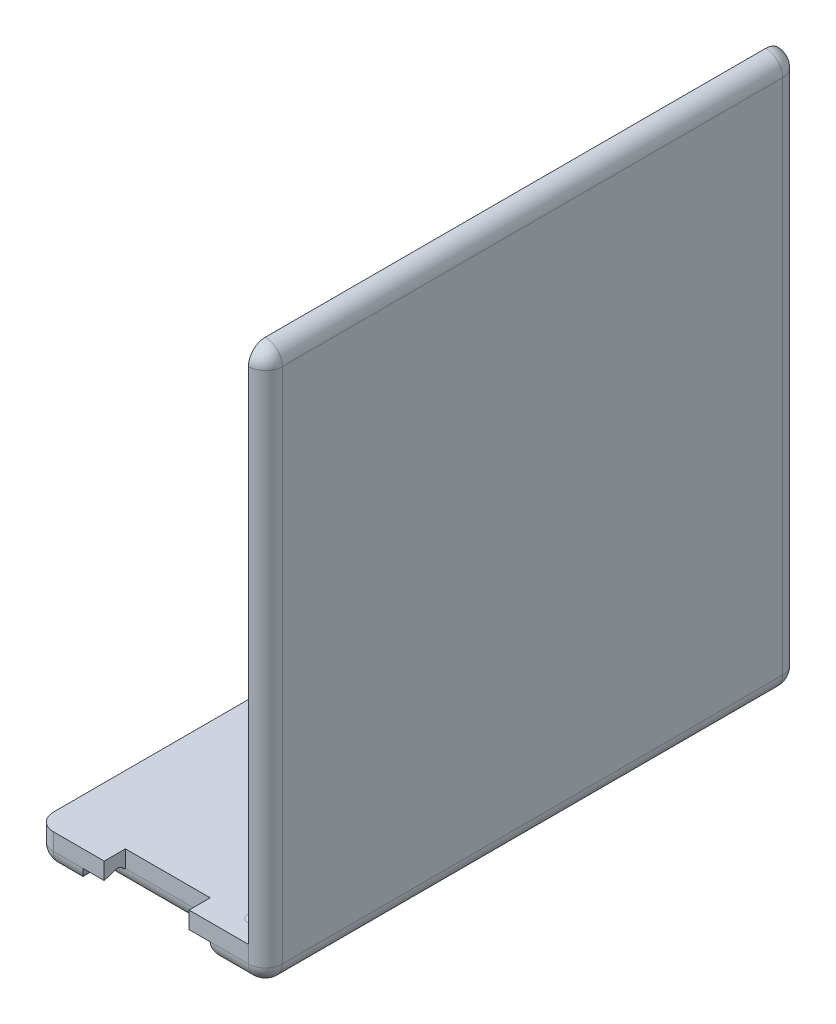
SolidWorks part; units mm, degrees
note: The reader was unsure of these and kept them because the rebuilt part matched: shared geometry of "Sketch6<3>".
ref_plane "Front Plane" through (0, 0, 0) normal (0, 0, 1) x (1, 0, 0)
ref_plane "Top Plane" through (0, 0, 0) normal (0, 1, 0) x (1, 0, 0)
ref_plane "Right Plane" through (0, 0, 0) normal (1, 0, 0) x (0, 0, -1)
sketch "Sketch1" plane through (0, 0, 0) normal (0, 1, 0) x (1, 0, 0)
  line L1 (0, 0) -> (-25, 0)
  line L2 (0, 0) -> (0, -63)
  line L3 (0, -63) -> (-25, -63)
  line L4 (-25, 0) -> (-25, -63)
  dimension "D1" = 63
  dimension "D2" = 25
extrude "Boss-Extrude1" add sketch "Sketch1" along normal blind 4
sketch "Sketch3" plane through (0, 0, 0) normal (1, 0, 0) x (0, 0, -1)
  line L1 (-63, 0) -> (0, 0)
  line L2 (-63, 0) -> (-63, 4)
  line L3 (-63, 4) -> (0, 4)
  line L4 (0, 0) -> (0, 4)
extrude "Boss-Extrude2" add sketch "Sketch3" along normal blind 2
sketch "Sketch4" plane through (0, 4, 0) normal (0, 1, 0) x (1, 0, 0)
  line L1 (2, -63) -> (0, -63)
  line L2 (2, -63) -> (2, 0)
  line L3 (2, 0) -> (0, 0)
  line L4 (0, -63) -> (0, 0)
extrude "Boss-Extrude3" add sketch "Sketch4" along normal blind 61
sketch "Sketch6" plane through (0, 0, 0) normal (0, -1, 0) x (1, 0, 0)
  line L0 (-25, 63) -> (2, 63) construction
  line L1 (-7, 63) -> (-17, 63)
  line L2 (-7, 63) -> (-7, 60.5)
  line L3 (-7, 60.5) -> (-17, 60.5)
  line L4 (-17, 63) -> (-17, 60.5)
  line L5 (2, 0) -> (-25, 0) construction
  line L6 (-7, 0) -> (-17, 0)
  line L7 (-7, 0) -> (-7, 2.5)
  line L8 (-7, 2.5) -> (-17, 2.5)
  line L9 (-17, 0) -> (-17, 2.5)
  line L10 (-25, 0) -> (-25, 63) construction
  dimension "D1" = 2.5
  dimension "D2" = 2.5
  dimension "D3" = 10
  dimension "D4" = 10
  dimension "D5" = 8
  dimension "D6" = 8
extrude "Cut-Extrude1" cut sketch "Sketch6" against normal through all contours L8 L9 L6 L7
extrude "Cut-Extrude2" cut sketch "Sketch6<3>" against normal blind 80 contours L3 L4 L1 L2
sketch "Sketch6<3>" plane through (0, 0, 0) normal (0, -1, 0) x (1, 0, 0) same geometry as "Sketch6"
sketch "Sketch8" plane through (0, 0, 63) normal (0, 0, 1) x (1, 0, 0)
  line L0 (-7, 0) -> (2, 0) construction
  line L1 (-4.5, 0) -> (-19.5, 0)
  line L2 (-4.5, 0) -> (-4.5, 2)
  line L3 (-4.5, 2) -> (-19.5, 2)
  line L4 (-19.5, 0) -> (-19.5, 2)
  line L5 (-25, 4) -> (-25, 0) construction
  dimension "D1" = 2
  dimension "D2" = 15
  dimension "D3" = 5.5
extrude "Cut-Extrude3" cut sketch "Sketch8" against normal blind 2.5
sketch "Sketch9" plane through (-4.5, 0, 0) normal (-1, 0, 0) x (0, 0, 1)
  line L0 (63, 0) -> (63, 2) construction
  line L1 (60.5, 2) -> (63, 2) construction
  line L2 (61.5, 2.5) -> (63, 2)
  line L3 (63, 2) -> (61.5, 2)
  line L4 (61.5, 2) -> (61.5, 2.5)
  circle A0 centre (61.5, 1.5) radius 1
  line M3 (63, 2) -> (60.5, 2)
  dimension "D1" = 2
  dimension "D2" = 1.5
  dimension "D3" = 0.5
extrude "Cut-Extrude5" cut sketch "Sketch9" along a picked direction on the side of the normal blind 15 contours A0 L3 M3 | L4 A0 M3
sketch "Sketch10" plane through (0, 0, 0) normal (0, -1, 0) x (1, 0, 0)
  line L0 (2, 31.5) -> (-25, 31.5) construction
  line L1 (2, 63) -> (2, 0) construction
  line L2 (-25, 0) -> (-25, 63) construction
  line L3 (-25, 31.5) -> (2, 31.5) construction
sketch "Sketch11" plane through (0, 0, 0) normal (0, 0, -1) x (-1, 0, 0)
  line L0 (-2, 0) -> (7, 0) construction
  line L1 (4.5, 0) -> (19.5, 0)
  line L2 (4.5, 0) -> (4.5, 2)
  line L3 (4.5, 2) -> (19.5, 2)
  line L4 (19.5, 0) -> (19.5, 2)
  line L5 (25, 4) -> (25, 0) construction
  dimension "D1" = 2
  dimension "D2" = 15
  dimension "D3" = 5.5
extrude "Cut-Extrude6" cut sketch "Sketch11" against normal blind 3 contours L2 L3 L4 L1
sketch "Sketch12" plane through (-4.5, 0, 0) normal (-1, 0, 0) x (0, 0, 1)
  line L0 (0, 0) -> (0, 2) construction
  line L1 (3, 2) -> (0, 2) construction
  line L2 (1.9, 2.5) -> (0, 2)
  line L3 (0, 2) -> (1.9, 2)
  line L4 (1.9, 2) -> (1.9, 2.5)
  circle A0 centre (1.9, 1.5) radius 1
  line M4 (3, 2) -> (0, 2)
  dimension "D1" = 2
  dimension "D2" = 1.9
  dimension "D3" = 0.5
extrude "Cut-Extrude7" cut sketch "Sketch12" along normal blind 15 contours A0 M4 | A0 L4 M4
fillet "Fillet6" radius 2 12 edges at (-19.5, 0, 1.5) (-22.25, 0, 0) (-25, 0, 31.5) (-22.25, 0, 63) (-19.5, 0, 61.75) (-12, 0, 60.5) (-4.5, 0, 61.75) (-1.25, 0, 63) (2, 0, 31.5) (-1.25, 0, 0) (-4.5, 0, 1.5) (-12, 0, 3)
fillet "Fillet7" radius 2 4 edges at (-24.4142, 0.5858, 0.5858) (-24.4142, 0.5858, 62.4142) (-25, 3, 0) (-25, 3, 63)
sketch "Sketch13" plane through (0, 4, 0) normal (0, 1, 0) x (1, 0, 0)
  line L6 (0, -4.25) -> (-1.5, -4.25)
  line L7 (0, 0) -> (0, -63) construction
  line L8 (-1.5, -4.25) -> (-1.5, -2.6)
  line L9 (-1.5, -2.6) -> (-2.7, -2.6)
  line L10 (-2.7, -2.6) -> (-2.7, -5.6)
  line L11 (-2.7, -5.6) -> (0, -5.6)
  line L12 (0, 0) -> (-7, 0) construction
  line L13 (0, -4.25) -> (0, -5.6)
  line L14 (0, -31.5) -> (-25.0562, -31.5) construction
  line L15 (-1.5, -60.4) -> (-2.7, -60.4)
  line L16 (-2.7, -60.4) -> (-2.7, -57.4)
  line L17 (-2.7, -57.4) -> (0, -57.4)
  line L18 (0, -58.75) -> (0, -57.4)
  line L19 (0, -58.75) -> (-1.5, -58.75)
  line L20 (-1.5, -58.75) -> (-1.5, -60.4)
  dimension "D1" = 1.5
  dimension "D2" = 1.2
  dimension "D3" = 2.6
  dimension "D4" = 3
  dimension "D5" = 1.35
extrude "Boss-Extrude4" add sketch "Sketch13" along normal blind 53
fillet "Fillet8" radius 0.4 24 edges at (-1.5, 4, 3.425) (0, 57, 4.925) (0, 57, 58.075) (-1.5, 4, 59.575) (-1.5, 30.5, 2.6) (-2.1, 57, 2.6) (-2.1, 4, 2.6) (-2.7, 30.5, 2.6) (-2.7, 57, 4.1) (-2.7, 4, 4.1) (-2.7, 30.5, 5.6) (-1.35, 57, 5.6) (0, 30.5, 5.6) (-1.35, 4, 5.6) (0, 30.5, 57.4) (-1.35, 57, 57.4) (-1.35, 4, 57.4) (-2.7, 30.5, 57.4) (-2.7, 57, 58.9) (-2.7, 4, 58.9) (-2.7, 30.5, 60.4) (-2.1, 57, 60.4) (-1.5, 30.5, 60.4) (-2.1, 4, 60.4)
fillet "Fillet9" radius 2 5 edges at (1.4142, 0.5858, 0.5858) (1.4142, 0.5858, 62.4142) (2, 65, 31.5) (2, 33.5, 0) (2, 33.5, 63)
sketch "Sketch15" plane through (0, 0, 0) normal (0, -1, 0) x (-1, 0, 0)
  line L0 (6, -38.5) -> (1, -31.625)
  line L1 (6, -46.5) -> (17, -46.5)
  line L2 (6, -46.5) -> (6, -38.5)
  line L3 (6, -38.5) -> (17, -38.5)
  line L4 (17, -46.5) -> (17, -38.5)
  line L5 (6, -46.5) -> (17, -38.5) construction
  line L6 (6, -38.5) -> (17, -46.5) construction
  line L7 (1, -31.625) -> (22, -31.625)
  line L8 (22, -31.625) -> (17, -38.5)
  line L9 (0, -2) -> (0, -61) construction
  line L10 (23, -61) -> (23, -2) construction
  line L12 (11.5, -31.625) -> (7.9645, -28.0895) construction
  line L13 (11.5, -31.625) -> (15.0355, -28.0895) construction
  line L14 (11.5, -31.625) -> (21.3995, -21.7255) construction
  line L15 (11.5, -31.625) -> (1.6005, -21.7255) construction
  line L16 (2.5, -58.5) -> (21.5, -58.5) construction
  line L17 (21.5, -5) -> (2.5, -5) construction
  arc A0 (7.9645, -28.0895) -> (15.0355, -28.0895) centre (11.5, -31.625) cw construction
  arc A1 (15.7426, -27.3824) -> (7.2574, -27.3824) centre (11.5, -31.625) ccw
  arc A2 (14.3284, -28.7966) -> (8.6716, -28.7966) centre (11.5, -31.625) ccw
  arc A3 (14.3284, -28.7966) -> (15.7426, -27.3824) centre (15.0355, -28.0895) ccw
  arc A4 (7.2574, -27.3824) -> (8.6716, -28.7966) centre (7.9645, -28.0895) ccw
  arc A5 (4.7287, -24.9617) -> (18.1633, -24.8537) centre (11.5, -31.625) cw construction
  arc A6 (18.8647, -24.1409) -> (4.0159, -24.2603) centre (11.5, -31.625) ccw
  arc A7 (17.4619, -25.5665) -> (5.4415, -25.6631) centre (11.5, -31.625) ccw
  arc A8 (17.4619, -25.5665) -> (18.8647, -24.1409) centre (18.1633, -24.8537) ccw
  arc A9 (4.0159, -24.2603) -> (5.4415, -25.6631) centre (4.7287, -24.9617) ccw
  arc A10 (1.6005, -21.7255) -> (21.3995, -21.7255) centre (11.5, -31.625) cw construction
  arc A11 (22.1066, -21.0184) -> (0.8934, -21.0184) centre (11.5, -31.625) ccw
  arc A12 (20.6924, -22.4326) -> (2.3076, -22.4326) centre (11.5, -31.625) ccw
  arc A13 (20.6924, -22.4326) -> (22.1066, -21.0184) centre (21.3995, -21.7255) ccw
  arc A14 (0.8934, -21.0184) -> (2.3076, -22.4326) centre (1.6005, -21.7255) ccw
  point P4 (11.5, -42.5)
  point P16 (11.5, -26.625)
  point P26 (11.4236, -22.1253)
  point P31 (11.5, -17.625)
  dimension "D10" = 2
  dimension "D12" = 2
  dimension "D13" = 2
  dimension "D14" = 8.5
  dimension "D15" = 13
  dimension "D19" = 12
  dimension "D20" = 26.625
  dimension "D1" = 21
  dimension "D2" = 1
  dimension "D3" = 1
  dimension "D4" = 6
  dimension "D5" = 11
  dimension "D6" = 8
  dimension "D7" = 6.875
  dimension "D8" = 45
  dimension "D9" = 45
  dimension "D11" = 5
  dimension "D16" = 45
  dimension "D17" = 45
  dimension "D18" = 11.5
extrude "Cut-Extrude8" cut sketch "Sketch15" against normal blind 2 and the other way through all contours L1 L4 L3 L2 | L8 L7 L0 L3 | A1 A4 A2 A3 | A6 A9 A7 A8 | A11 A14 A12 A13
